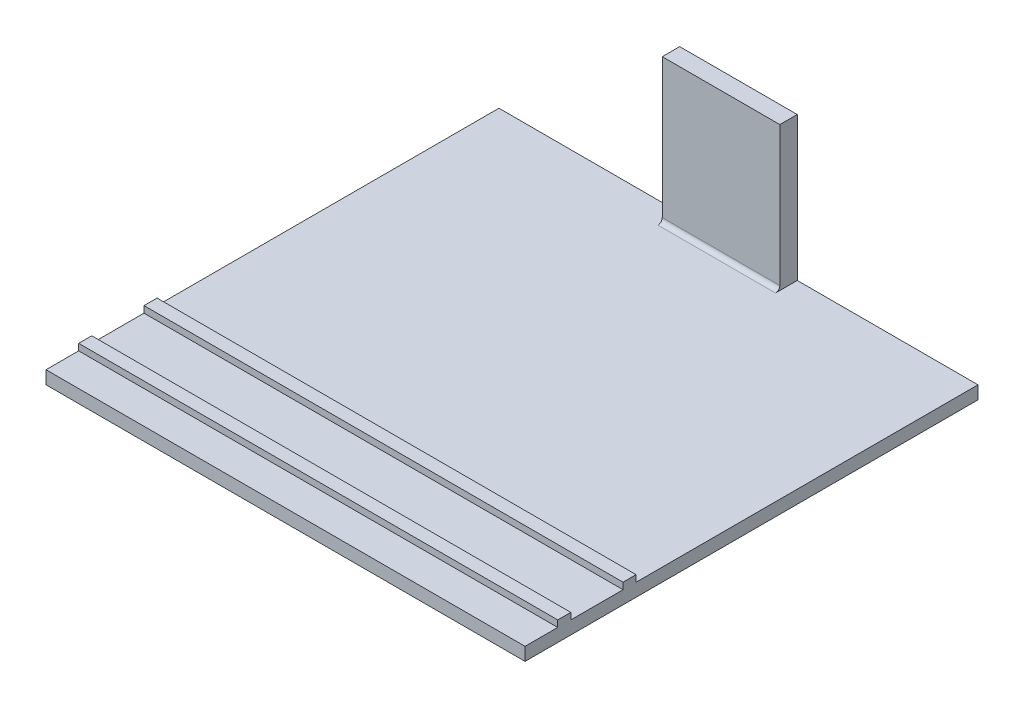
SolidWorks part; units mm, degrees
ref_plane "Piano frontale" through (0, 0, 0) normal (0, 0, 1) x (1, 0, 0)
ref_plane "Piano superiore" through (0, 0, 0) normal (0, 1, 0) x (1, 0, 0)
ref_plane "Piano destro" through (0, 0, 0) normal (1, 0, 0) x (0, 0, -1)
sketch "Schizzo1" plane through (0, 0, 0) normal (0, 0, 1) x (1, 0, 0)
  line L1 (0, 0) -> (27, 0)
  line L2 (0, 0) -> (0, -36)
  line L3 (0, -36) -> (27, -36)
  line L4 (27, 0) -> (27, -36)
  dimension "D1" = 27
  dimension "D2" = 36
extrude "Estrusione-Estrusione1" add sketch "Schizzo1" along normal blind 4
sketch "Schizzo3" plane through (0, 0, 4) normal (0, 0, 1) x (1, 0, 0)
  line L0 (27, -36) -> (27, 0) construction
  line L1 (0, -36) -> (27, -36)
  line L2 (0, -36) -> (0, -33)
  line L3 (0, -33) -> (27, -33)
  line L4 (27, -36) -> (27, -33)
  dimension "D1" = 3
extrude "Estrusione-Estrusione2" add sketch "Schizzo3" along normal blind 100
fillet "Raccordo1" radius 1 1 edges at (13.5, -33, 4)
sketch "Schizzo5" plane through (27, 0, 0) normal (1, 0, 0) x (0, 0, -1)
  line L0 (0, -36) -> (0, 0) construction
  line L1 (-104, -36) -> (0, -36)
  line L2 (-104, -36) -> (-104, -33)
  line L3 (-104, -33) -> (0, -33)
  line L4 (0, -36) -> (0, -33)
  line L9 (-104, -33) -> (-5, -33) construction
extrude "Estrusione-Estrusione3" add sketch "Schizzo5" along normal blind 170 and the other way blind 150
sketch "Schizzo6" plane through (-123, 0, 0) normal (-1, 0, 0) x (0, 0, 1)
  line L0 (78.5, -33) -> (78.5, -32.25)
  line L1 (0, -33) -> (104, -33) construction
  line L3 (78.5, -32.25) -> (78.5, -31.5)
  line L4 (78.5, -31.5) -> (81.5, -31.5)
  line L5 (81.5, -31.5) -> (81.5, -32.25)
  line L6 (93.5, -33) -> (96.5, -33)
  line L7 (81.5, -32.25) -> (81.5, -33)
  line L8 (93.5, -33) -> (93.5, -31.5)
  line L9 (93.5, -31.5) -> (96.5, -31.5)
  line L10 (96.5, -33) -> (96.5, -31.5)
  line M11 (104, -33) -> (0, -33)
  dimension "D1" = 1.5
  dimension "D2" = 3
  dimension "D3" = 3
  dimension "D4" = 1.5
  dimension "D5" = 12
  dimension "D6" = 7.5
extrude "Estrusione-Estrusione4" add sketch "Schizzo6" against normal blind 320 contours L7 L5 L4 L3 L0 M11 | L10 L9 L8 M11 region at (-123, -32.25, 95) region at (-123, -32.25, 80)
sketch "Schizzo7" plane through (0, -33, 0) normal (0, 1, 0) x (1, 0, 0)
  line L0 (197, -104) -> (-123, -104) construction
  line L1 (-123, 0) -> (-58, 0)
  line L2 (-123, 0) -> (-123, -104)
  line L3 (-123, -104) -> (-58, -104)
  line L4 (-58, 0) -> (-58, -104)
  line L6 (197, 0) -> (132, 0)
  line L7 (197, 0) -> (197, -104)
  line L8 (197, -104) -> (132, -104)
  line L9 (132, 0) -> (132, -104)
  dimension "D1" = 65
extrude "Taglio-Estrusione1" cut sketch "Schizzo7" against normal blind 10 and the other way blind 10
sketch "Schizzo8" plane through (0, -33, 0) normal (0, 1, 0) x (1, 0, 0)
  line L0 (132, 0) -> (132, -78.5) construction
  line L1 (27, 0) -> (132, 0) construction
  circle A0 centre (104, -24) radius 13.5
  dimension "D1" = 27
  dimension "D2" = 28
  dimension "D3" = 24
extrude "Taglio-Estrusione2" cut sketch "Schizzo8" against normal blind 10
sketch "Schizzo9" plane through (0, -33, 0) normal (0, 1, 0) x (1, 0, 0)
  line L0 (-41.5, 0) -> (68.5, 0)
  line L1 (-41.5, 0) -> (-41.5, -104)
  line L2 (68.5, 0) -> (68.5, -104)
  line L3 (-41.5, -104) -> (68.5, -104)
  line L7 (132, -104) -> (-58, -104) construction
  line L9 (27, 0) -> (132, 0) construction
  line L10 (132, 0) -> (132, -78.5) construction
  line L12 (27, 0) -> (0, 0) construction
  point P6 (13.5, 0)
  point P11 (0, 0)
  point P14 (13.5, 0)
  dimension "D1" = 110
extrude "Taglio-Estrusione3" cut sketch "Schizzo9" against normal blind 10 and the other way blind 10 flip side to cut
